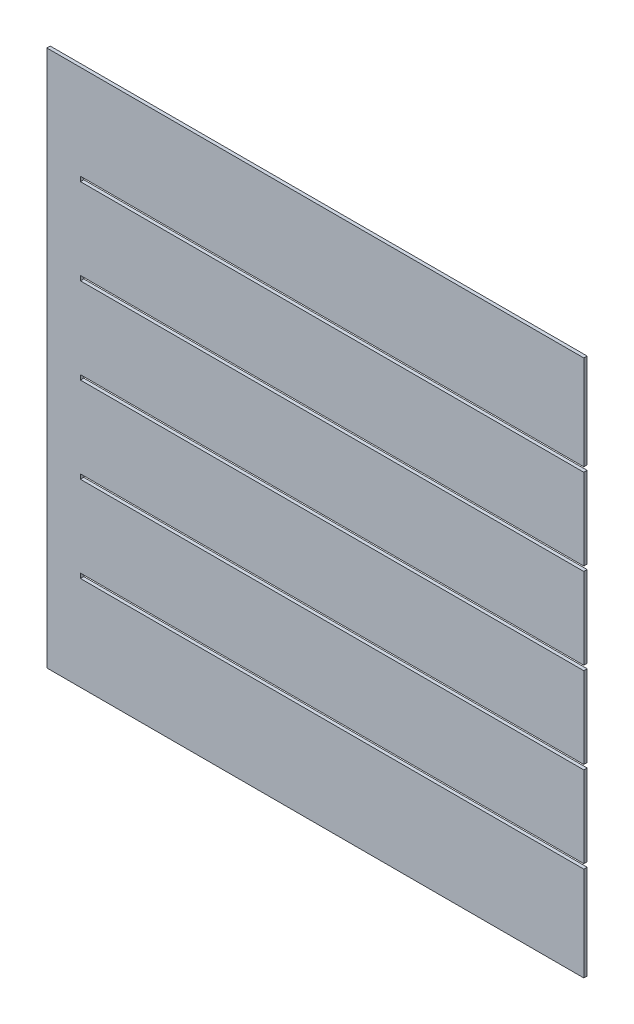
SolidWorks part; units mm, degrees
ref_plane "前视基准面" through (0, 0, 0) normal (0, 0, 1) x (1, 0, 0)
ref_plane "上视基准面" through (0, 0, 0) normal (0, 1, 0) x (1, 0, 0)
ref_plane "右视基准面" through (0, 0, 0) normal (1, 0, 0) x (0, 0, -1)
sketch "草图1" plane through (0, 0, 0) normal (0, 0, 1) x (1, 0, 0)
  line L0 (-75, 51.8686) -> (75, 51.8686)
  line L5 (75, 79.9686) -> (75, 51.8686)
  line L6 (75, 50.4686) -> (75, 26.2686)
  line L7 (-75, 50.4686) -> (75, 50.4686)
  line L8 (75, 24.8686) -> (75, 0.6686)
  line L9 (-75, 50.4686) -> (-75, 51.8686)
  line L10 (-75, 51.8686) -> (-75, 51.1686) construction
  line L11 (-75, 51.1686) -> (75, 51.1686) construction
  line L12 (-75, 51.8686) -> (75, 51.8686)
  line L13 (-75, 24.8686) -> (-75, 26.2686)
  line L14 (75, -0.7314) -> (75, -24.9314)
  line L15 (75, -26.3314) -> (75, -50.5314)
  line L16 (-65, 51.8686) -> (75, 51.8686)
  line L17 (-65, 50.4686) -> (75, 50.4686)
  line L18 (75, -51.9314) -> (75, -80.0314)
  line L19 (-65, 51.8686) -> (75, 51.8686)
  line L20 (-75, -0.7314) -> (-75, 0.6686)
  line L21 (-65, 51.1686) -> (75, 51.1686) construction
  line L22 (75, 79.9686) -> (-85, 79.9686)
  line L23 (-85, 79.9686) -> (-85, -80.0314)
  line L24 (-65, 26.2686) -> (75, 26.2686)
  line L25 (-65, 24.8686) -> (75, 24.8686)
  line L27 (-65, 26.2686) -> (75, 26.2686)
  line L29 (-65, 25.5686) -> (75, 25.5686) construction
  line L30 (-85, -80.0314) -> (75, -80.0314)
  line L32 (-65, 0.6686) -> (75, 0.6686)
  line L33 (-65, -0.7314) -> (75, -0.7314)
  line L35 (-65, 0.6686) -> (75, 0.6686)
  line L37 (-65, -0.0314) -> (75, -0.0314) construction
  line L45 (-65, -25.6314) -> (75, -25.6314) construction
  line L47 (-75, -26.3314) -> (-75, -24.9314)
  line L50 (-75, -0.0314) -> (-85, -0.0314) construction
  line L54 (-75, -51.9314) -> (-75, -50.5314)
  line L56 (-75, 26.2686) -> (75, 26.2686)
  line L57 (-75, 24.8686) -> (75, 24.8686)
  line L59 (-75, 26.2686) -> (75, 26.2686)
  line L61 (-75, 25.5686) -> (75, 25.5686) construction
  line L64 (-75, 0.6686) -> (75, 0.6686)
  line L65 (-75, -0.7314) -> (75, -0.7314)
  line L67 (-75, 0.6686) -> (75, 0.6686)
  line L69 (-75, -0.0314) -> (75, -0.0314) construction
  line L72 (-75, -24.9314) -> (75, -24.9314)
  line L73 (-75, -26.3314) -> (75, -26.3314)
  line L75 (-75, -24.9314) -> (75, -24.9314)
  line L77 (-75, -25.6314) -> (75, -25.6314) construction
  line L80 (-75, -50.5314) -> (75, -50.5314)
  line L81 (-75, -51.9314) -> (75, -51.9314)
  line L83 (-75, -50.5314) -> (75, -50.5314)
  line L85 (-75, -51.2314) -> (75, -51.2314) construction
  line L101 (-65, -26.3314) -> (75, -26.3314) [skipped]
  line L102 (-65, -24.9314) -> (75, -24.9314) [skipped]
  line L103 (-65, -24.9314) -> (75, -24.9314) [skipped]
  line L105 (-65, -50.5314) -> (75, -50.5314) [skipped]
  line L106 (-65, -50.5314) -> (75, -50.5314) [skipped]
  line L107 (-65, -51.9314) -> (75, -51.9314) [skipped]
  line L108 (-65, -51.2314) -> (75, -51.2314) construction
  point P0 (0, 0)
  point P3 (-85, -0.0314)
  dimension "D1" = 160
  dimension "D3" = 1.4
  dimension "D5" = 2
  dimension "D7" = 25.6
  dimension "D6" = 5
extrude "凸台-拉伸1" add sketch "草图1" along normal blind 1 contours L81 L54 L80 L73 L47 L72 L33 L65 L20 L64 L32 L25 L57 L13 L56 L24 L7 region at (-77.2627, 51.1686, 0)
